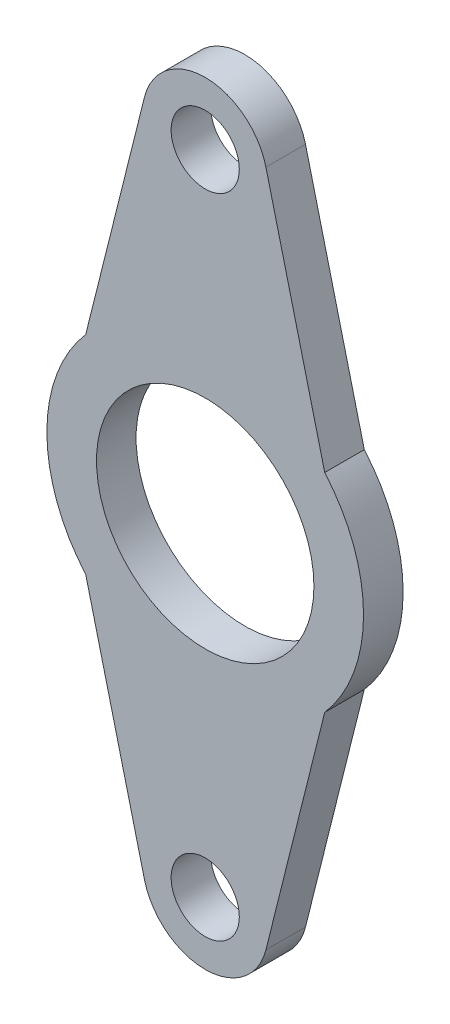
SolidWorks part; units mm, degrees
ref_plane "Front Plane" through (0, 0, 0) normal (0, 0, 1) x (1, 0, 0)
ref_plane "Top Plane" through (0, 0, 0) normal (0, 1, 0) x (1, 0, 0)
ref_plane "Right Plane" through (0, 0, 0) normal (1, 0, 0) x (0, 0, -1)
sketch "Sketch1" plane through (0, 0, 0) normal (0, 0, 1) x (1, 0, 0)
  line L0 (9.7409, 54.3696) -> (19.1721, 16.661)
  line L1 (-9.7409, 54.3696) -> (-19.1721, 16.661)
  line L2 (0, 0) -> (71.0753, 0) construction
  line L3 (9.7409, -54.3696) -> (19.1721, -16.661)
  line L4 (-9.7409, -54.3696) -> (-19.1721, -16.661)
  circle A0 centre (0, 0) radius 17.442
  circle A1 centre (0, 0) radius 25.4
  circle A2 centre (0, 51.9333) radius 10.0409
  circle A3 centre (0, -51.9333) radius 10.0409
  circle A4 centre (0, 51.9333) radius 5.4689
  circle A5 centre (0, 51.9333) radius 4.9609 construction
  circle A6 centre (0, 51.9333) radius 4.9609 construction
  circle A7 centre (0, -51.9333) radius 5.4689
  dimension "D1" = 5.08
  dimension "D2" = 50.8
  dimension "D3" = 0.508
extrude "Boss-Extrude1" add sketch "Sketch1" along normal blind 6.35 contours A2 L1 A1 L0 | A2 | A1 A0 | A3 L3 A1 L4 | A3 region at (0, 33.2758, 0) region at (9.6838, 53.1259, 0) region at (23.1192, 8.6419, 0) region at (0, -33.2758, 0) region at (0, -61.6903, 0)
